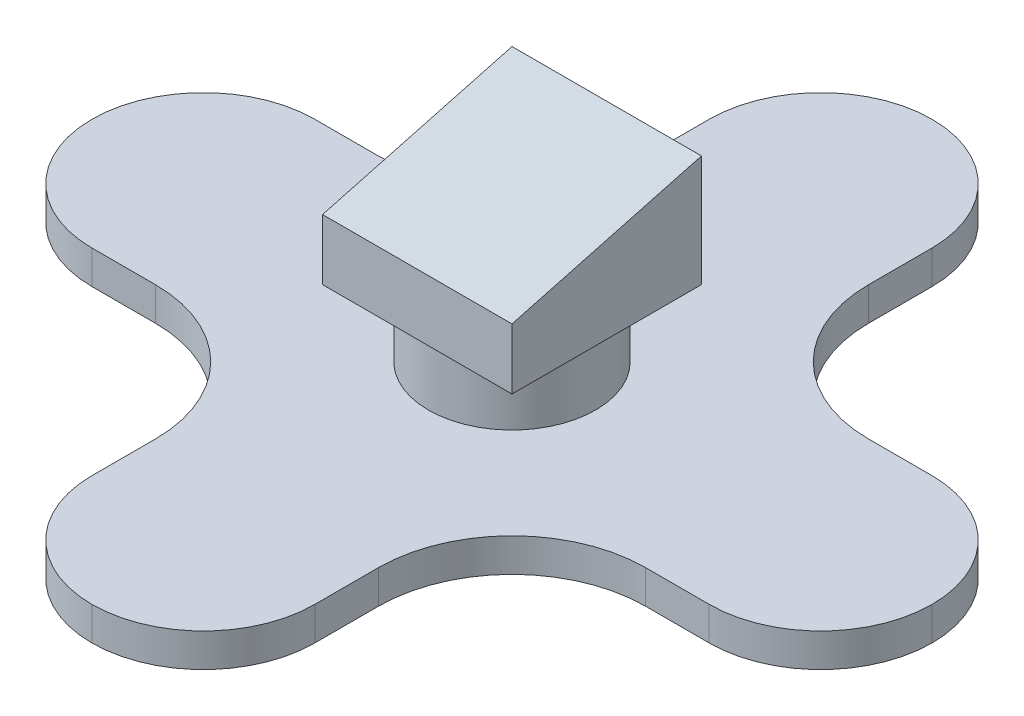
SolidWorks part; units mm, degrees
ref_plane "Front Plane" through (0, 0, 0) normal (0, 0, 1) x (1, 0, 0)
ref_plane "Top Plane" through (0, 0, 0) normal (0, 1, 0) x (1, 0, 0)
ref_plane "Right Plane" through (0, 0, 0) normal (1, 0, 0) x (0, 0, -1)
sketch "Sketch1" plane through (0, 0, 0) normal (0, 1, 0) x (1, 0, 0)
  circle A0 centre (0, 0) radius 2.5
  circle A1 centre (0, 0) radius 3.75
  dimension "D1" = 5
  dimension "D2" = 7.5
extrude "Boss-Extrude1" add sketch "Sketch1" along normal blind 3 contours A1
sketch "Sketch2" plane through (0, 0, 0) normal (0, -1, 0) x (1, 0, 0)
  line L1 (-5, 18.8481) -> (5, 18.8481)
  line L2 (-5, 18.8481) -> (-5, -18.8481)
  line L3 (-5, -18.8481) -> (5, -18.8481)
  line L4 (5, 18.8481) -> (5, -18.8481)
  line L5 (-5, 18.8481) -> (5, -18.8481) construction
  line L6 (-5, -18.8481) -> (5, 18.8481) construction
  line L7 (-18.8481, 5) -> (18.8481, 5)
  line L8 (-18.8481, 5) -> (-18.8481, -5)
  line L9 (-18.8481, -5) -> (18.8481, -5)
  line L10 (18.8481, 5) -> (18.8481, -5)
  line L11 (-18.8481, 5) -> (18.8481, -5) construction
  line L12 (-18.8481, -5) -> (18.8481, 5) construction
  circle A0 centre (0, 0) radius 19.5
  dimension "D1" = 39
  dimension "D2" = 10
  dimension "D3" = 10
sketch "Sketch5" plane through (0, 3, 0) normal (0, 1, 0) x (1, 0, 0)
  line L1 (-4.25, -4.25) -> (4.25, -4.25)
  line L2 (-4.25, -4.25) -> (-4.25, 4.25)
  line L3 (-4.25, 4.25) -> (4.25, 4.25)
  line L4 (4.25, -4.25) -> (4.25, 4.25)
  line L5 (-4.25, -4.25) -> (4.25, 4.25) construction
  line L6 (-4.25, 4.25) -> (4.25, -4.25) construction
  point P0 (0, 0)
  dimension "D1" = 8.5
  dimension "D2" = 8.5
extrude "Boss-Extrude3" add sketch "Sketch5" along normal blind 5
sketch "Sketch19" plane through (-4.25, 0, 0) normal (-1, 0, 0) x (0, 0, 1)
  line L0 (-4.25, 8) -> (4.25, 8)
  line L1 (4.25, 8) -> (4.25, 5.7224)
  line L2 (4.25, 8) -> (4.25, 3) construction
  line L3 (4.25, 5.7224) -> (-4.25, 8)
  dimension "D1" = 75
extrude "Cut-Extrude4" cut sketch "Sketch19" against normal blind 30
extrude "Boss-Extrude4" add sketch "Sketch2" along normal blind 1.5 contours L10 L7 L4 L9 | L8 L9 L2 L7 | L2 L3 L4 L1 region at (-11.924, 0, 0) region at (11.924, 0, 0)
fillet "Fillet1" radius 5 8 edges at (18.8481, -0.75, -5) (5, -0.75, -18.8481) (-5, -0.75, -18.8481) (-18.8481, -0.75, -5) (-18.8481, -0.75, 5) (18.8481, -0.75, 5) (5, -0.75, 18.8481) (-5, -0.75, 18.8481)
fillet "Fillet2" radius 6 4 edges at (-5, -0.75, 5) (-5, -0.75, -5) (5, -0.75, -5) (5, -0.75, 5)
